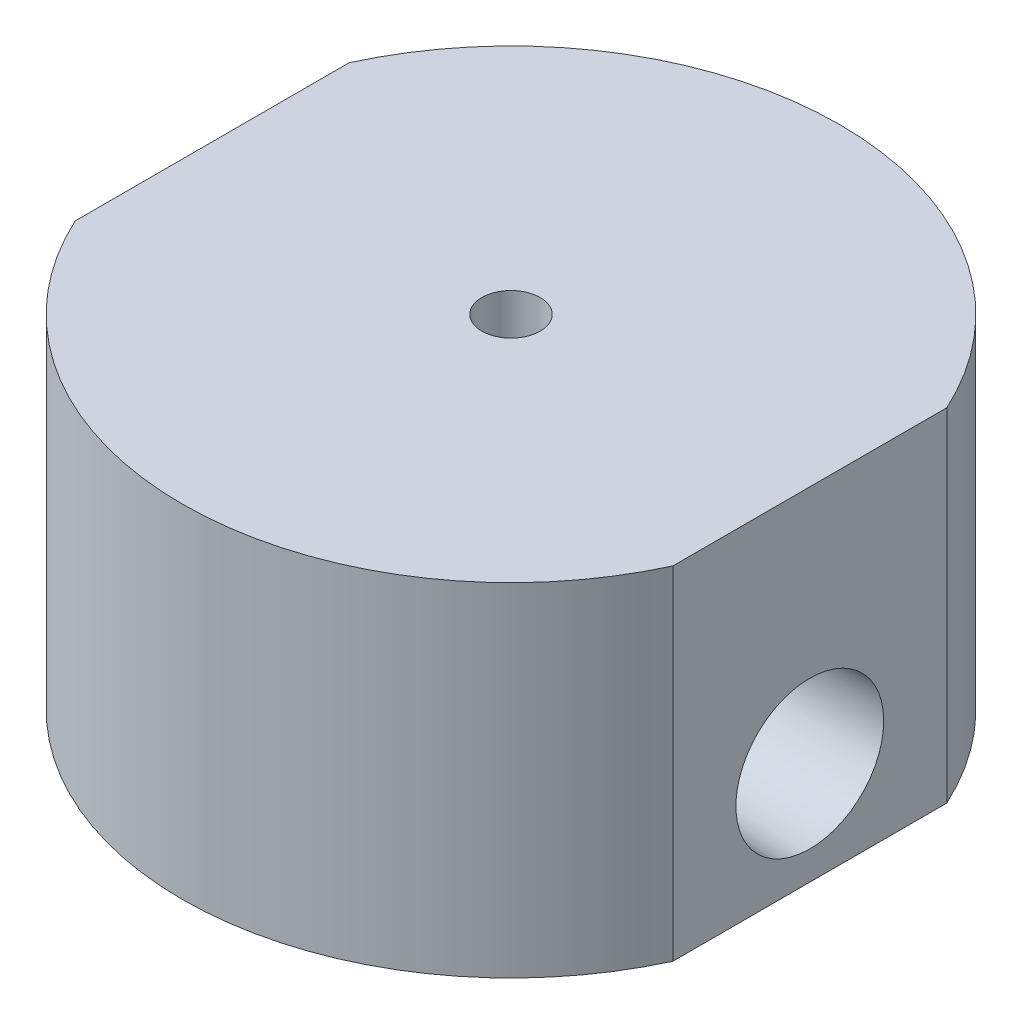
SolidWorks part; units mm, degrees
material "AISI Type 316L stainless steel"
ref_plane "Front Plane" through (0, 0, 0) normal (0, 0, 1) x (1, 0, 0)
ref_plane "Top Plane" through (0, 0, 0) normal (0, 1, 0) x (1, 0, 0)
ref_plane "Right Plane" through (0, 0, 0) normal (1, 0, 0) x (0, 0, -1)
sketch "Sketch1" plane through (0, 0, 0) normal (0, 0, 1) x (1, 0, 0)
  line L0 (0, 0) -> (0, 31.75) construction
  line L1 (0, 31.75) -> (-30.48, 31.75)
  line L2 (-30.48, 31.75) -> (-30.48, 0)
  line L3 (-30.48, 0) -> (-17.145, 0)
  line L4 (-17.145, 0) -> (-17.145, 19.05)
  line L5 (-17.145, 19.05) -> (-13.97, 19.05)
  line L6 (-4.7625, 9.8425) -> (0, 9.8425)
  line L7 (0, 31.75) -> (0, 9.8425)
  arc A0 (-13.97, 19.05) -> (-4.7625, 9.8425) centre (-13.97, 9.8425) cw
  dimension "D1" = 19.05
  dimension "D2" = 12.7
  dimension "D3" = 60.96
  dimension "D4" = 34.29
  dimension "D5" = 9.525
  dimension "D6" = 3.175
revolve "Revolve1" add sketch "Sketch1" angle 360 about L0
hole_wizard "1/4-28 Tapped Hole1" positions "Sketch2" profile "Sketch3" tap size "1/4-28" standard "ANSI Inch" end condition through all
sketch "Sketch2" plane through (0, 31.75, 0) normal (0, 1, 0) x (1, 0, 0)
  point P0 (0, 0)
sketch "Sketch3" plane through (0, 31.75, 0) normal (1, 0, 0) x (0, 0, 1)
  line L0 (0, 0) -> (0, 31.75)
  line L1 (0, 31.75) -> (2.7051, 31.75)
  line L2 (2.7051, 31.75) -> (2.7051, 0)
  line L5 (2.7051, 0) -> (0, 0)
  line L11 (0, -6.35) -> (0, 107.95) construction
  dimension "Thru Tap Drill Dia." = 5.4102
  dimension "Thru Tap Drill Depth" = 31.75
cosmetic thread "Hole Thread1" parameters "D2"=6.35
sketch "Sketch4" plane through (0, 0, 0) normal (0, 1, 0) x (1, 0, 0)
  line L0 (0, 0) -> (0, 17.6947) construction
  line L1 (-27.7081, 12.7) -> (-53.1081, 12.7)
  line L2 (-27.7081, 12.7) -> (-27.7081, -12.7)
  line L3 (-27.7081, -12.7) -> (-53.1081, -12.7)
  line L4 (-53.1081, 12.7) -> (-53.1081, -12.7)
  line L5 (53.1081, 12.7) -> (53.1081, -12.7)
  line L6 (27.7081, -12.7) -> (53.1081, -12.7)
  line L7 (27.7081, 12.7) -> (27.7081, -12.7)
  line L8 (27.7081, 12.7) -> (53.1081, 12.7)
  circle A0 centre (0, 0) radius 30.48 construction
  dimension "D1" = 25.4
extrude "flats" cut sketch "Sketch4" along normal through all
hole_wizard "1/4 NPT Tapped Hole1" positions "Sketch5" profile "Sketch6" size "1/4" standard "ANSI Inch"
sketch "Sketch5" plane through (27.7081, 0, 0) normal (1, 0, 0) x (0, 0, -1)
  line L0 (-12.7, 19.05) -> (12.7, 19.05) construction
  line L1 (-12.7, 31.75) -> (-12.7, 0) construction
  line L2 (12.7, 31.75) -> (12.7, 0) construction
  line L4 (-17.145, 19.05) -> (17.145, 19.05) construction
  line L5 (-12.7, 0) -> (12.7, 19.05) construction
  point P0 (0, 9.525)
  point P20 (0, 9.525)
sketch "Sketch6" plane through (27.7081, 9.525, 0) normal (0, 1, 0) x (0, 0, -1)
  line L0 (0, 0) -> (0, 20.6143)
  line L1 (5.5626, 17.272) -> (0, 20.6143)
  line L2 (-5.5626, 17.272) -> (0, 20.6143) construction
  line L3 (5.5626, 17.272) -> (5.5626, 9.906)
  line L4 (5.5626, 9.906) -> (6.558, 9.906)
  line L5 (6.558, 9.906) -> (6.8546, 0)
  line L6 (-6.558, 9.906) -> (-6.8546, 0) construction
  line L7 (6.8546, 0) -> (0, 0)
  line L8 (0, -6.35) -> (0, 107.95) construction
  line L11 (-5.5626, 9.906) -> (-6.558, 9.906) construction
  dimension "Tap Drill Dia." = 11.1252
  dimension "Tap Drill Depth" = 17.272
  dimension "Thread Dia." = 13.7092
  dimension "Thread Angle" = 3.43
  dimension "Thread Depth" = 9.906
  dimension "Drill Angle" = 118
mirror "Mirror1" about plane through (0, 0, 0) normal (1, 0, 0) of "1/4 NPT Tapped Hole1"
fillet "Fillet1" radius 1.5875 1 edges at (17.145, 19.05, 0)
